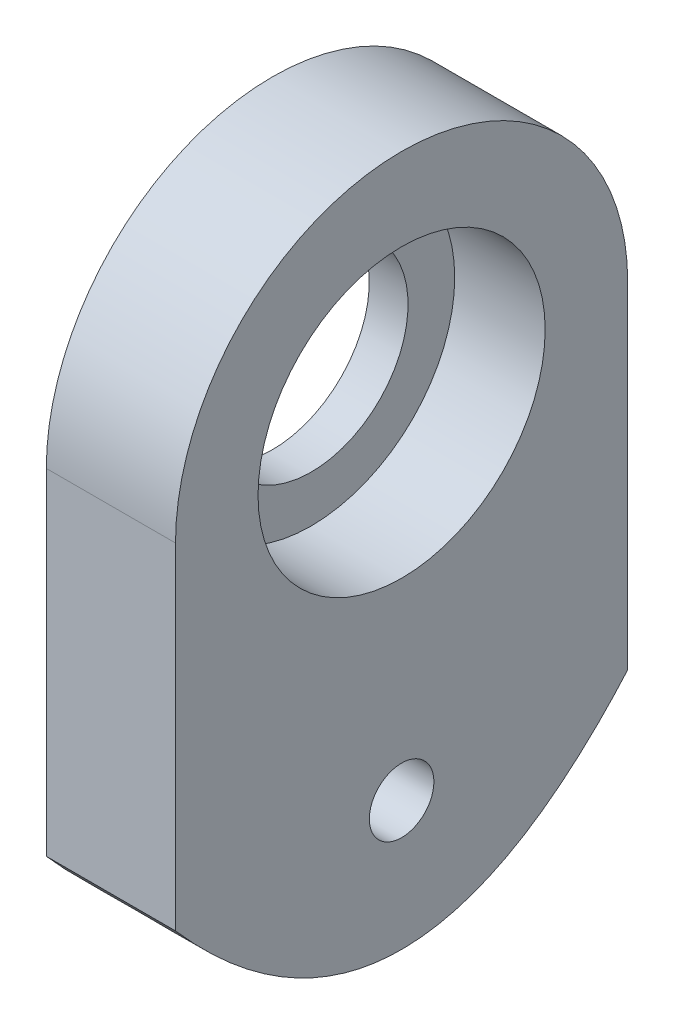
SolidWorks part; units mm, degrees
ref_plane "Alzado" through (0, 0, 0) normal (0, 0, 1) x (1, 0, 0)
ref_plane "Planta" through (0, 0, 0) normal (0, 1, 0) x (1, 0, 0)
ref_plane "Vista lateral" through (0, 0, 0) normal (1, 0, 0) x (0, 0, -1)
sketch "Croquis1" plane through (0, 0, 0) normal (1, 0, 0) x (0, 0, -1)
  line L3 (-3.5368, 13.8741) -> (-13.7837, -3.8741)
  line L4 (-10.247, -10) -> (10.247, -10)
  line L5 (13.7837, -3.8741) -> (3.5368, 13.8741)
  line L7 (17.5, 0) -> (17.5, -26)
  line L8 (-17.5, 0) -> (-17.5, -26)
  arc A10 (11.8234, -9.2308) -> (13.9058, -5.624) centre (0, 0) ccw
  arc A11 (2.0824, 14.8548) -> (-2.0824, 14.8548) centre (0, 0) ccw
  arc A13 (-13.7837, -3.8741) -> (-13.9058, -5.624) centre (-12.0517, -4.8741) ccw
  arc A14 (-10.247, -10) -> (-11.8234, -9.2308) centre (-10.247, -8) cw
  arc A15 (10.247, -10) -> (11.8234, -9.2308) centre (10.247, -8) ccw
  arc A16 (13.7837, -3.8741) -> (13.9058, -5.624) centre (12.0517, -4.8741) cw
  arc A17 (3.5368, 13.8741) -> (2.0824, 14.8548) centre (1.8047, 12.8741) ccw
  arc A18 (-3.5368, 13.8741) -> (-2.0824, 14.8548) centre (-1.8047, 12.8741) cw
  arc A19 (-14.3624, -4.3269) -> (-11.8234, -9.2308) centre (0, 0) ccw
  arc A20 (17.5, 0) -> (-17.5, 0) centre (0, 0) ccw
  circle A21 centre (0, -26) radius 26 construction
  circle A22 centre (0, -26) radius 2.5
  spline S0 degree 2 poles (-17.5, -26) (0, -46) (17.5, -26) knots 0 0 0 1 1 1
  dimension "D1" = 30
  dimension "D2" = 35
  dimension "D3" = 26
  dimension "D4" = 5
extrude "Saliente-Extruir2" add sketch "Croquis1" along normal blind 10 contours L8 S0 L7 A20 A19 A13 L3 A18 A11 A17 L5 A16 A10 A15 L4 A14 A22 region at (0, -13.039, 0)
ref_axis "Eje1" through (10, -26, 0) along (-1, 0, 0)
ref_axis "Eje2" through (10, 0, 0) along (-1, 0, 0)
sketch "Croquis2" plane through (0, 0, 0) normal (-1, 0, 0) x (0, 0, 1)
  line L0 (-11.0196, -1.4341) -> (-5.702, -9.5381)
  line L4 (6.7518, -8.8262) -> (11.1112, -0.169)
  line L7 (4.2678, 10.2603) -> (-5.4092, 9.7071)
  circle A0 centre (0, 0) radius 11.1125
  circle A1 centre (0, 0) radius 17.5
  arc M3 (13.9058, -5.624) -> (11.8234, -9.2308) centre (0, 0) cw
  arc M4 (11.8234, -9.2308) -> (10.247, -10) centre (10.247, -8) cw
  line M5 (10.247, -10) -> (-10.247, -10)
  arc M6 (-10.247, -10) -> (-11.8234, -9.2308) centre (-10.247, -8) cw
  arc M7 (-11.8234, -9.2308) -> (-13.9058, -5.624) centre (0, 0) cw
  arc M8 (-13.9058, -5.624) -> (-13.7837, -3.8741) centre (-12.0517, -4.8741) cw
  line M9 (-13.7837, -3.8741) -> (-3.5368, 13.8741)
  arc M10 (-3.5368, 13.8741) -> (-2.0824, 14.8548) centre (-1.8047, 12.8741) cw
  arc M11 (-2.0824, 14.8548) -> (2.0824, 14.8548) centre (0, 0) cw
  arc M12 (2.0824, 14.8548) -> (3.5368, 13.8741) centre (1.8047, 12.8741) cw
  line M13 (3.5368, 13.8741) -> (13.7837, -3.8741)
  arc M14 (13.7837, -3.8741) -> (13.9058, -5.624) centre (12.0517, -4.8741) cw
  arc M17 (17.5, 0) -> (-17.5, 0) centre (0, 0) ccw
  dimension "D1" = 22.225
extrude "Saliente-Extruir3" add sketch "Croquis2" against normal blind 10 contours A1 A0 M17 M13 M14 M3 M4 M5 M6 M7 M8 M9 M10 M11 M12 | A0 M9 M8 M7 M6 M5 | A0 M5 M4 M3 M14 M13 | A0 M13 M12 M11 M10 M9 region at (0, -6.2371, -10.8029) region at (0, 12.4742, 0) region at (0, -6.2371, 10.8029) region at (0, -17.005, 0)
sketch "Croquis3" plane through (0, 0, 0) normal (-1, 0, 0) x (0, 0, 1)
  line L0 (-11.0835, 0.8029) -> (-6.2371, 9.1971)
  line L1 (6.2371, 9.1971) -> (11.0835, 0.8029)
  line L2 (4.8464, -10) -> (-4.8464, -10)
  circle A0 centre (0, 0) radius 11.1125
  arc M2 (-6.2371, 9.1971) -> (6.2371, 9.1971) centre (0, 0) cw
  line M3 (6.2371, 9.1971) -> (11.0835, 0.8029)
  arc M4 (11.0835, 0.8029) -> (4.8464, -10) centre (0, 0) cw
  line M5 (4.8464, -10) -> (-4.8464, -10)
  arc M6 (-4.8464, -10) -> (-11.0835, 0.8029) centre (0, 0) cw
  line M7 (-11.0835, 0.8029) -> (-6.2371, 9.1971)
extrude "Cortar-Extruir1" cut sketch "Croquis3" against normal blind 10 contours A0 M7 | A0 M3 | A0 M5 | M2 M7 M6 M5 M4 M3 region at (0, 5.2235, -9.0473) region at (0, 0, 0) region at (0, -10.447, 0) region at (0, 5.2235, 9.0473)
sketch "Croquis4" plane through (0, 0, 0) normal (-1, 0, 0) x (0, 0, 1)
  circle A0 centre (0, 0) radius 11.1125
  circle A1 centre (0, 0) radius 7.5
  dimension "D1" = 15
extrude "Saliente-Extruir4" add sketch "Croquis4" against normal blind 3 contours A0 | A1
